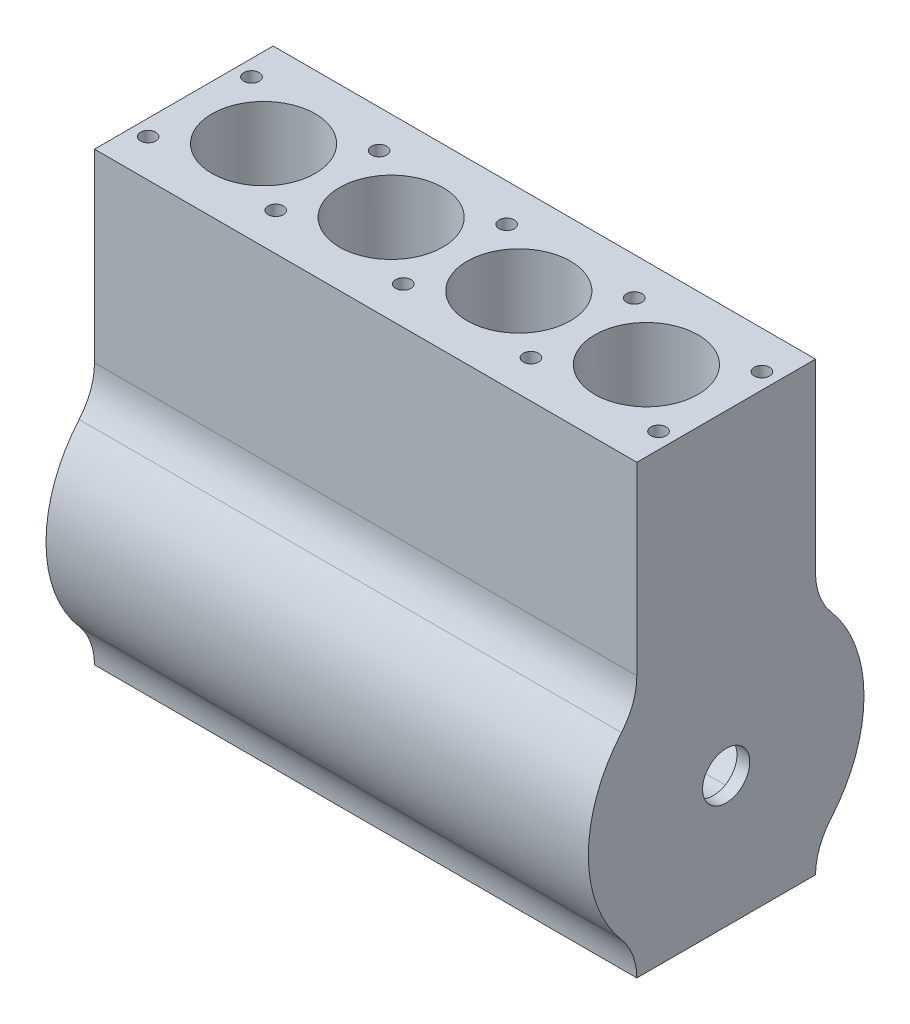
SolidWorks part; units mm, degrees
ref_plane "Front Plane" through (0, 0, 0) normal (0, 0, 1) x (1, 0, 0)
ref_plane "Top Plane" through (0, 0, 0) normal (0, 1, 0) x (1, 0, 0)
ref_plane "Right Plane" through (0, 0, 0) normal (1, 0, 0) x (0, 0, -1)
sketch "Sketch1" plane through (0, 0, 0) normal (0, 1, 0) x (1, 0, 0)
  line L0 (0, 0) -> (62.5, 0)
  line L1 (62.5, 0) -> (162.5, 0)
  line L2 (162.5, 0) -> (262.5, 0)
  line L3 (262.5, 0) -> (362.5, 0)
  line L4 (362.5, 0) -> (425, 0)
  line L5 (0, 0) -> (0, 70) construction
  line L6 (425, 0) -> (425, -70) construction
  line L8 (0, 70) -> (425, 70)
  line L9 (0, 70) -> (0, -70)
  line L10 (0, -70) -> (425, -70)
  line L11 (425, 70) -> (425, -70)
  circle A0 centre (62.5, 0) radius 40.5015
  circle A1 centre (162.5, 0) radius 40.5015
  circle A2 centre (262.5, 0) radius 40.5015
  circle A3 centre (362.5, 0) radius 40.5015
  dimension "D6" = 81.003
  dimension "D7" = 81.003
  dimension "D8" = 81.003
  dimension "D9" = 81.003
  dimension "D1" = 62.5
  dimension "D2" = 100
  dimension "D3" = 100
  dimension "D4" = 100
  dimension "D5" = 62.5
  dimension "D10" = 70
  dimension "D11" = 70
  dimension "D12" = 425
extrude "Boss-Extrude1" add sketch "Sketch1" along normal blind 350 contours A3 L3 A2 L2 A1 L1 A0 L0 L9 L10 L11 L4 | A3 L4 L11 L8 L9 L0 A0 L1 A1 L2 A2 L3 region at (212.5, 0, -44.4413) region at (212.5, 0, 44.4413)
sketch "Sketch2" plane through (0, 0, 0) normal (0, -1, 0) x (1, 0, 0)
  line L14 (415, -60) -> (415, 60)
  line L15 (10, -60) -> (415, -60)
  line L16 (10, 60) -> (10, -60)
  line L17 (415, 60) -> (10, 60)
  line L18 (415, -60) -> (415, 60)
  line L19 (10, -60) -> (415, -60)
  line L20 (10, 60) -> (10, -60)
  line L21 (415, 60) -> (10, 60)
  dimension "D1" = 10
extrude "Cut-Extrude1" cut sketch "Sketch2" against normal blind 250
sketch "Sketch3" plane through (0, 0, 0) normal (-1, 0, 0) x (0, 0, 1)
  circle A0 centre (0, 102.3197) radius 18.5
  dimension "D1" = 37
extrude "Cut-Extrude2" cut sketch "Sketch3" against normal blind 425
sketch "Sketch5" plane through (0, 0, 0) normal (-1, 0, 0) x (0, 0, 1)
  line L0 (-70, 184.5633) -> (-70, 20.0762)
  line L1 (-70, 350) -> (-70, 0) construction
  line L3 (70, 184.5633) -> (70, 20.0762)
  line L5 (70, 350) -> (70, 0) construction
  circle A0 centre (0, 102.3197) radius 108
  dimension "D1" = 216
extrude "Boss-Extrude4" add sketch "Sketch5" against normal blind 425 contours L1 A0 | A0 region at (0, 102.3197, -85.4554) region at (0, 102.3197, 85.4554)
ref_plane "Plane2" through (10, 0, 0) normal (-1, 0, 0) x (0, 0, 1)
sketch "Sketch7" plane through (10, 0, 0) normal (-1, 0, 0) x (0, 0, 1)
  circle A0 centre (0, 102.3197) radius 99
  dimension "D1" = 198
extrude "Cut-Extrude4" cut sketch "Sketch7" against normal blind 405
fillet "Fillet1" radius 20 4 edges at (212.5, 23.5733, -60) (212.5, 23.5733, 60) (212.5, 181.0661, -60) (212.5, 181.0661, 60)
fillet "Fillet2" radius 50 4 edges at (212.5, 20.0762, -70) (212.5, 20.0762, 70) (212.5, 184.5633, 70) (212.5, 184.5633, -70)
sketch "Sketch8" plane through (0, 350, 0) normal (0, 1, 0) x (1, 0, 0)
  line L0 (62.5, 40.5015) -> (362.5, 40.5015) construction
  line L1 (62.5, -40.5015) -> (362.5, -40.5015) construction
  line L2 (62.5, 0) -> (162.5, 0) construction
  line L3 (162.5, 0) -> (262.5, 0) construction
  line L4 (262.5, 0) -> (362.5, 0) construction
  line L5 (112.5, -40.5015) -> (112.5, 40.5015) construction
  line L6 (212.5, -40.5015) -> (212.5, 40.5015) construction
  line L7 (312.5, -40.5015) -> (312.5, 40.5015) construction
  line L8 (62.5, 40.5015) -> (12.5, 40.5015) construction
  line L9 (62.5, -40.5015) -> (12.5, -40.5015) construction
  line L10 (362.5, 40.5015) -> (412.5, 40.5015) construction
  line L11 (362.5, -40.5015) -> (412.5, -40.5015) construction
  circle A0 centre (62.5, 0) radius 40.5015 construction
  circle A1 centre (362.5, 0) radius 40.5015 construction
  circle A2 centre (112.5, 40.5015) radius 6
  circle A3 centre (112.5, -40.5015) radius 6
  circle A4 centre (212.5, -40.5015) radius 6
  circle A5 centre (212.5, 40.5015) radius 6
  circle A6 centre (312.5, -40.5015) radius 6
  circle A7 centre (312.5, 40.5015) radius 6
  circle A8 centre (12.5, 40.5015) radius 6
  circle A9 centre (12.5, -40.5015) radius 6
  circle A10 centre (412.5, -40.5015) radius 6
  circle A11 centre (412.5, 40.5015) radius 6
  point P17 (112.5, 0)
  point P20 (212.5, 0)
  point P23 (312.5, 0)
  dimension "D4" = 12
  dimension "D5" = 12
  dimension "D6" = 12
  dimension "D7" = 12
  dimension "D8" = 12
  dimension "D9" = 12
  dimension "D14" = 12
  dimension "D15" = 12
  dimension "D16" = 12
  dimension "D17" = 12
  dimension "D1" = 100
  dimension "D2" = 100
  dimension "D3" = 100
  dimension "D10" = 50
  dimension "D11" = 50
  dimension "D12" = 50
  dimension "D13" = 50
extrude "Cut-Extrude5" cut sketch "Sketch8" against normal blind 80 contours A9 | A8 | A2 | A3 | A4 | A5 | A7 | A6 | A10 | A11 region at (112.5, 350, -40.5015) region at (112.5, 350, 40.5015) region at (212.5, 350, 40.5015) region at (212.5, 350, -40.5015) region at (312.5, 350, 40.5015) region at (312.5, 350, -40.5015) region at (12.5, 350, -40.5015) region at (12.5, 350, 40.5015) region at (412.5, 350, 40.5015) region at (412.5, 350, -40.5015)
